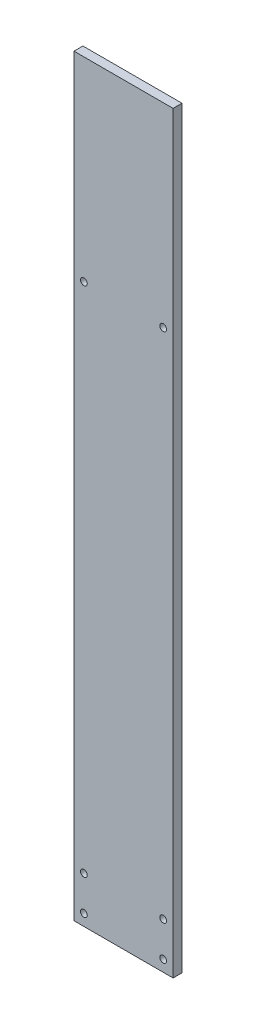
SolidWorks part; units mm, degrees
ref_plane "Front Plane" through (0, 0, 0) normal (0, 0, 1) x (1, 0, 0)
ref_plane "Top Plane" through (0, 0, 0) normal (0, 1, 0) x (1, 0, 0)
ref_plane "Right Plane" through (0, 0, 0) normal (1, 0, 0) x (0, 0, -1)
sketch "Sketch1" plane through (0, 0, 0) normal (0, 0, 1) x (1, 0, 0)
  line L0 (-325.3006, 181.5669) -> (-35.3006, 181.5669) construction
  line L1 (-230.3006, 181.5669) -> (-130.3006, 181.5669)
  line L2 (-230.3006, 181.5669) -> (-230.3006, -578.4331)
  line L3 (-230.3006, -578.4331) -> (-130.3006, -578.4331)
  line L4 (-130.3006, 181.5669) -> (-130.3006, -578.4331)
  line L5 (-33.3006, -578.4331) -> (-70.3006, -578.4331) construction
  line L6 (-180.3006, 181.5669) -> (-180.3006, -578.4331) construction
  line L7 (-230.3006, -198.4331) -> (-180.3006, -198.4331) construction
  line L8 (-180.3006, -198.4331) -> (-130.3006, -198.4331) construction
  dimension "D1" = 100
extrude "Boss-Extrude1" add sketch "Sketch1" along normal blind 9
hole_wizard "M8 Tapped Hole" positions "Sketch2" profile "Sketch3" tap size "M8" standard "ISO" end condition through all
sketch "Sketch2" plane through (-171.5962, -73.097, 9) normal (0, 0, 1) x (1, 0, 0)
  point P0 (-48.7044, -458.8361)
  point P3 (-48.7044, -493.8361)
  point P6 (31.2956, -493.8361)
  point P9 (31.2956, -458.8361)
  point P12 (31.2956, 58.0784)
  point P15 (-48.7044, 58.0784)
sketch "Sketch3" plane through (-220.3006, -531.9331, 9) normal (1, 0, 0) x (0, -1, 0)
  line L0 (0, 0) -> (0, 9)
  line L1 (0, 9) -> (3.4, 9)
  line L2 (3.4, 9) -> (3.4, 0)
  line L3 (3.4, 0) -> (0, 0)
  line L4 (0, -6.35) -> (0, 107.95) construction
  dimension "Thread Major Dia." = 6.8
  dimension "Thru Tap Drill Depth" = 9
